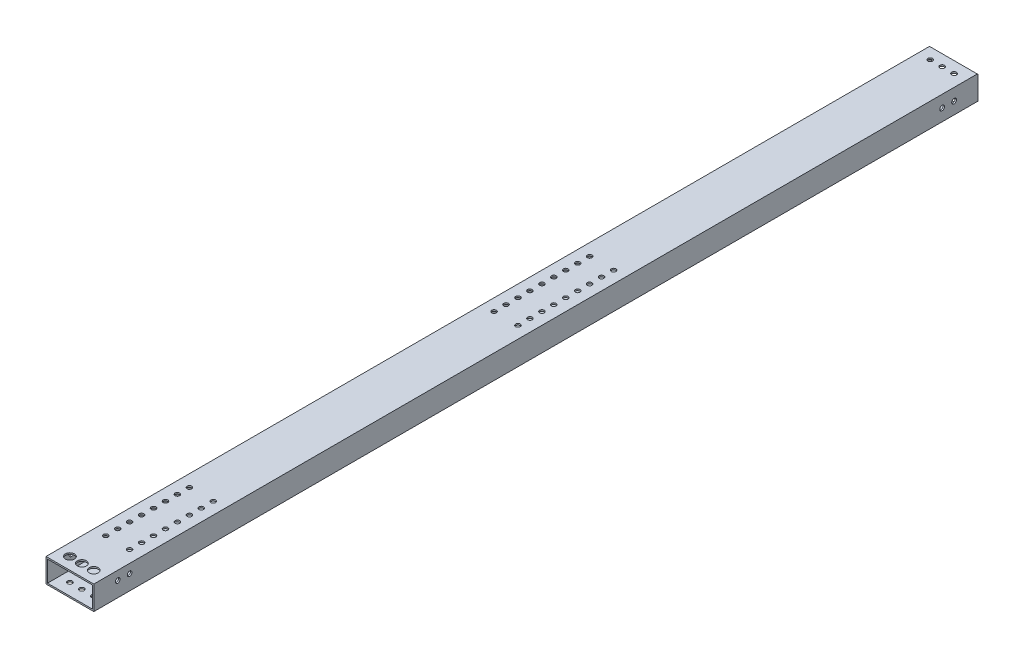
SolidWorks part; units mm, degrees
material "6061-T6 (SS)"
ref_plane "Front Plane" through (0, 0, 0) normal (0, 0, 1) x (1, 0, 0)
ref_plane "Top Plane" through (0, 0, 0) normal (0, 1, 0) x (1, 0, 0)
ref_plane "Right Plane" through (0, 0, 0) normal (1, 0, 0) x (0, 0, -1)
sketch "Sketch1" plane through (0, 0, 0) normal (0, 0, 1) x (1, 0, 0)
  line L0 (-23.8125, 11.1125) -> (23.8125, 11.1125)
  line L1 (-25.4, -12.7) -> (25.4, -12.7)
  line L2 (-25.4, -12.7) -> (-25.4, 12.7)
  line L3 (-25.4, 12.7) -> (25.4, 12.7)
  line L4 (25.4, -12.7) -> (25.4, 12.7)
  line L5 (-25.4, -12.7) -> (25.4, 12.7) construction
  line L6 (-25.4, 12.7) -> (25.4, -12.7) construction
  line L7 (23.8125, -11.1125) -> (23.8125, 11.1125)
  line L8 (-23.8125, -11.1125) -> (23.8125, -11.1125)
  line L9 (-23.8125, -11.1125) -> (-23.8125, 11.1125)
  point P0 (0, 0)
  dimension "D1" = 50.8
  dimension "D2" = 25.4
  dimension "D3" = 1.5875
extrude "Boss-Extrude1" add sketch "Sketch1" along normal mid plane 939.8
sketch "Sketch4" plane through (0, 12.7, 0) normal (0, 1, 0) x (1, 0, 0)
  line L0 (25.4, -469.9) -> (-25.4, -469.9) construction
  circle A0 centre (-12.7, -457.2) radius 4.826
  circle A1 centre (0, -457.2) radius 4.826
  circle A2 centre (12.7, -457.2) radius 4.826
  dimension "D1" = 9.652
  dimension "D2" = 12.7
  dimension "D3" = 12.7
  dimension "D4" = 12.7
extrude "Cut-Extrude3" cut sketch "Sketch4" against normal up to surface (1.5875 mm away) contours A0 | A1 | A2 region at (-12.7, 12.7, 457.2) region at (0, 12.7, 457.2) region at (12.7, 12.7, 457.2) up to face at (0, 11.1125, 0)
sketch "Sketch5" plane through (0, -12.7, 0) normal (0, -1, 0) x (1, 0, 0)
  circle A0 centre (-12.7, 457.2) radius 4.826 construction
  circle A1 centre (0, 457.2) radius 4.826 construction
  circle A2 centre (12.7, 457.2) radius 4.826 construction
  circle A3 centre (-12.7, 457.2) radius 4.826
  circle A4 centre (0, 457.2) radius 4.826
  circle A5 centre (12.7, 457.2) radius 4.826
  circle A6 centre (-12.7, 457.2) radius 2.5527
  circle A7 centre (0, 457.2) radius 2.5527
  circle A8 centre (12.7, 457.2) radius 2.5527
  dimension "D1" = 5.1054
extrude "Cut-Extrude4" cut sketch "Sketch5" against normal up to surface (1.5875 mm away) contours A8 | A7 | A6 region at (-12.7, -12.7, 457.2) region at (0, -12.7, 457.2) region at (12.7, -12.7, 457.2) up to face at (0, -11.1125, 0)
sketch "Sketch6" plane through (0, -12.7, 0) normal (0, -1, 0) x (1, 0, 0)
  line L0 (-25.4, -469.9) -> (25.4, -469.9) construction
  circle A0 centre (-12.7, -457.2) radius 2.5527
  circle A1 centre (0, -457.2) radius 2.5527
  circle A2 centre (12.7, -457.2) radius 2.5527
  dimension "D1" = 5.1054
  dimension "D2" = 12.7
  dimension "D3" = 12.7
  dimension "D4" = 12.7
extrude "Cut-Extrude5" cut sketch "Sketch6" against normal through all contours A2 | A1 | A0 region at (-12.7, -12.7, -457.2) region at (0, -12.7, -457.2) region at (12.7, -12.7, -457.2)
sketch "Sketch7" plane through (25.4, 0, 0) normal (1, 0, 0) x (0, 0, -1)
  line L0 (-469.9, -12.7) -> (-469.9, 12.7) construction
  line L2 (469.9, -12.7) -> (469.9, 12.7) construction
  line L3 (-469.9, -12.7) -> (469.9, -12.7) construction
  circle A0 centre (-457.2, 3.175) radius 2.4892
  circle A1 centre (-444.5, 3.175) radius 2.4892
  circle A2 centre (-431.8, 3.175) radius 2.4892
  circle A3 centre (-419.1, 3.175) radius 2.4892
  circle A4 centre (457.2, 0) radius 2.5527
  circle A5 centre (444.5, 0) radius 2.5527
  circle A6 centre (431.8, 0) radius 2.5527
  dimension "D1" = 4.9784
  dimension "D7" = 5.1054
  dimension "D8" = 12.7
  dimension "D2" = 12.7
  dimension "D3" = 12.7
  dimension "D4" = 12.7
  dimension "D5" = 12.7
  dimension "D6" = 15.875
  dimension "D9" = 12.7
  dimension "D10" = 12.7
  dimension "D11" = 12.7
extrude "Cut-Extrude6" cut sketch "Sketch7" against normal through all contours A6 | A5 | A1 | A2 region at (25.4, 3.175, 444.5) region at (25.4, 3.175, 431.8) region at (25.4, 0, -444.5) region at (25.4, 0, -431.8)
sketch "Sketch10" plane through (0, 12.7, 0) normal (0, 1, 0) x (1, 0, 0)
  line L1 (25.4, -469.9) -> (-25.4, -469.9) construction
  line L3 (-25.4, -469.9) -> (-25.4, 469.9) construction
  circle A0 centre (-12.7, -419.1) radius 2.4892
  circle A5 centre (12.7, -419.1) radius 2.4892
  circle A6 centre (-12.7, -406.4) radius 2.4892
  circle A7 centre (12.7, -406.4) radius 2.4892
  circle A8 centre (-12.7, -393.7) radius 2.4892
  circle A9 centre (12.7, -393.7) radius 2.4892
  circle A10 centre (-12.7, -381) radius 2.4892
  circle A11 centre (12.7, -381) radius 2.4892
  circle A12 centre (-12.7, -368.3) radius 2.4892
  circle A13 centre (12.7, -368.3) radius 2.4892
  circle A14 centre (-12.7, -355.6) radius 2.4892
  circle A15 centre (12.7, -355.6) radius 2.4892
  circle A16 centre (-12.7, -342.9) radius 2.4892
  circle A17 centre (12.7, -342.9) radius 2.4892
  circle A18 centre (-12.7, -330.2) radius 2.4892
  circle A19 centre (12.7, -330.2) radius 2.4892
  circle A20 centre (-12.7, -6.35) radius 2.4892
  circle A21 centre (12.7, -6.35) radius 2.4892
  circle A22 centre (-12.7, 6.35) radius 2.4892
  circle A23 centre (12.7, 6.35) radius 2.4892
  circle A24 centre (-12.7, 19.05) radius 2.4892
  circle A25 centre (12.7, 19.05) radius 2.4892
  circle A26 centre (-12.7, 31.75) radius 2.4892
  circle A27 centre (12.7, 31.75) radius 2.4892
  circle A28 centre (-12.7, 44.45) radius 2.4892
  circle A29 centre (12.7, 44.45) radius 2.4892
  circle A30 centre (-12.7, 57.15) radius 2.4892
  circle A31 centre (12.7, 57.15) radius 2.4892
  circle A32 centre (-12.7, 69.85) radius 2.4892
  circle A33 centre (12.7, 69.85) radius 2.4892
  circle A34 centre (-12.7, 82.55) radius 2.4892
  circle A35 centre (12.7, 82.55) radius 2.4892
  circle A36 centre (-12.7, 95.25) radius 2.4892
  circle A37 centre (12.7, 95.25) radius 2.4892
  dimension "D1" = 25.4
  dimension "D3" = 4.9784
  dimension "D2" = 12.7
  dimension "D4" = 50.8
  dimension "D5" = 12.7
  dimension "D6" = 323.85
  dimension "D8" = 12.7
  dimension "D9" = 9
extrude "Cut-Extrude8" cut sketch "Sketch10" against normal up to next (1.5875 mm away)
chamfer "Chamfer1" distance 0.762 angle 45 1 edges at (0, 12.7, -469.9)
